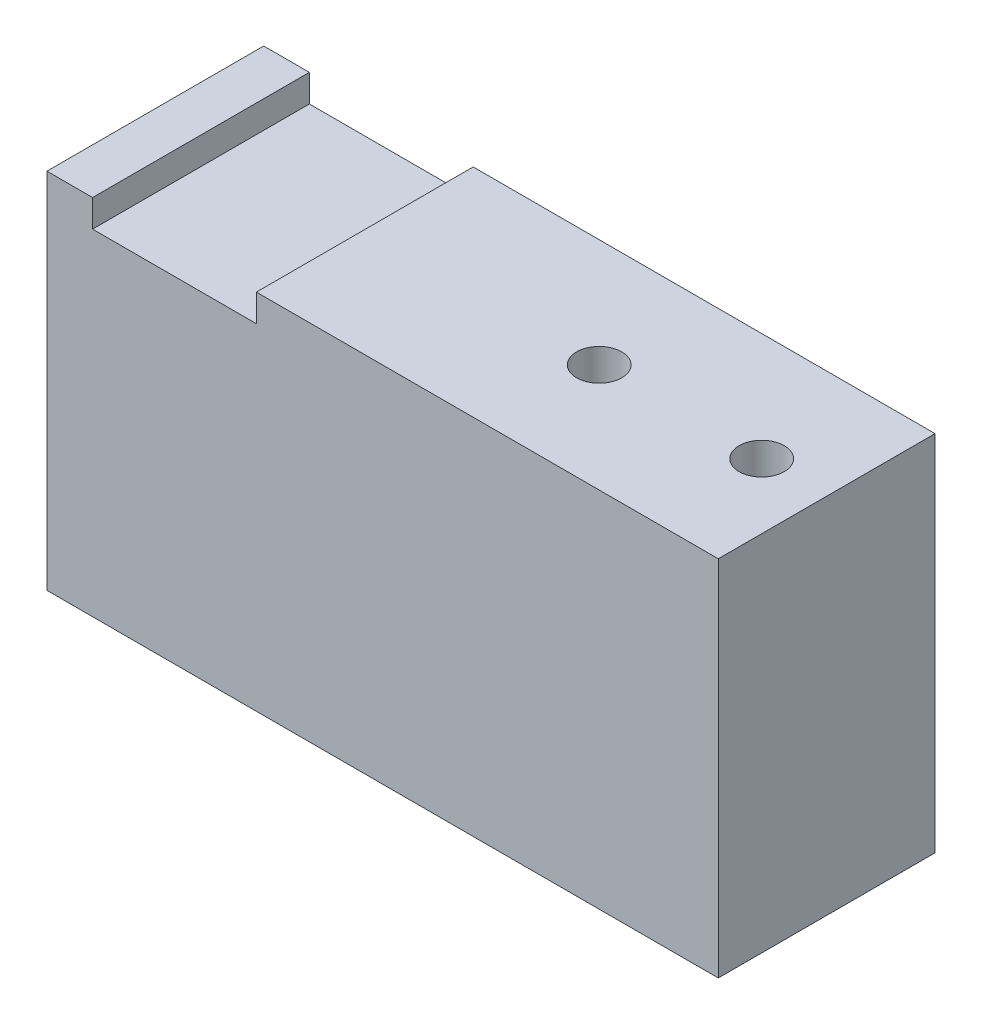
SolidWorks part; units mm, degrees
ref_plane "Спереди" through (0, 0, 0) normal (0, 0, 1) x (1, 0, 0)
ref_plane "Сверху" through (0, 0, 0) normal (0, 1, 0) x (1, 0, 0)
ref_plane "Справа" through (0, 0, 0) normal (1, 0, 0) x (0, 0, -1)
other "Configuration Table"
sketch "основание" plane through (0, 0, 0) normal (0, 1, 0) x (1, 0, 0)
  line L1 (-31.25, -10.09) -> (31.25, -10.09)
  line L2 (-31.25, -10.09) -> (-31.25, 10.09)
  line L3 (-31.25, 10.09) -> (31.25, 10.09)
  line L4 (31.25, -10.09) -> (31.25, 10.09)
  line L5 (-31.25, -10.09) -> (31.25, 10.09) construction
  line L6 (-31.25, 10.09) -> (31.25, -10.09) construction
  point P0 (0, 0)
  dimension "D1" = 20.18
  dimension "D2" = 62.5
extrude "Бобышка-Вытянуть1" add sketch "основание" along normal blind 33.8
sketch "Эскиз5" plane through (0, 33.8, 0) normal (0, 1, 0) x (1, 0, 0)
sketch "Эскиз6" plane through (0, 33.8, 0) normal (0, 1, 0) x (1, 0, 0)
  line L0 (31.25, 10.09) -> (-31.25, 10.09) construction
  line L1 (-27, 10.09) -> (-11.75, 10.09)
  line L2 (-27, 10.09) -> (-27, -10.09)
  line L3 (-27, -10.09) -> (-11.75, -10.09)
  line L4 (-11.75, 10.09) -> (-11.75, -10.09)
  line L5 (-31.25, -10.09) -> (31.25, -10.09) construction
  dimension "D1" = 15.25
  dimension "D2" = 4.25
extrude "Вырез-Вытянуть1" cut sketch "Эскиз6" against normal blind 2.55
sketch "Эскиз7" plane through (0, 0, 0) normal (0, -1, 0) x (1, 0, 0)
  line L0 (0, 0) -> (0, 33.5331) construction
  line L1 (0, 0) -> (57.6127, 0) construction
  circle A0 centre (17, 0) radius 2.5
  circle A1 centre (-17, 0) radius 2.5
  dimension "D1" = 5
  dimension "D2" = 17
extrude "Вырез-Вытянуть2" cut sketch "Эскиз7" against normal blind 15
sketch "Эскиз8" plane through (0, 33.8, 0) normal (0, 1, 0) x (1, 0, 0)
  line L0 (0, 0) -> (59.9314, 0) construction
  line L1 (31.25, -10.09) -> (31.25, 10.09) construction
  circle A0 centre (25.2, 0) radius 2.1
  circle A1 centre (10.07, 0) radius 2.1
  point P7 (27.3, 0)
  point P8 (12.17, 0)
  point P11 (23.1, 0)
  dimension "D1" = 4.2
  dimension "D2" = 4.2
  dimension "D3" = 3.95
  dimension "D4" = 10.93
extrude "Вырез-Вытянуть3" cut sketch "Эскиз8" against normal blind 15
